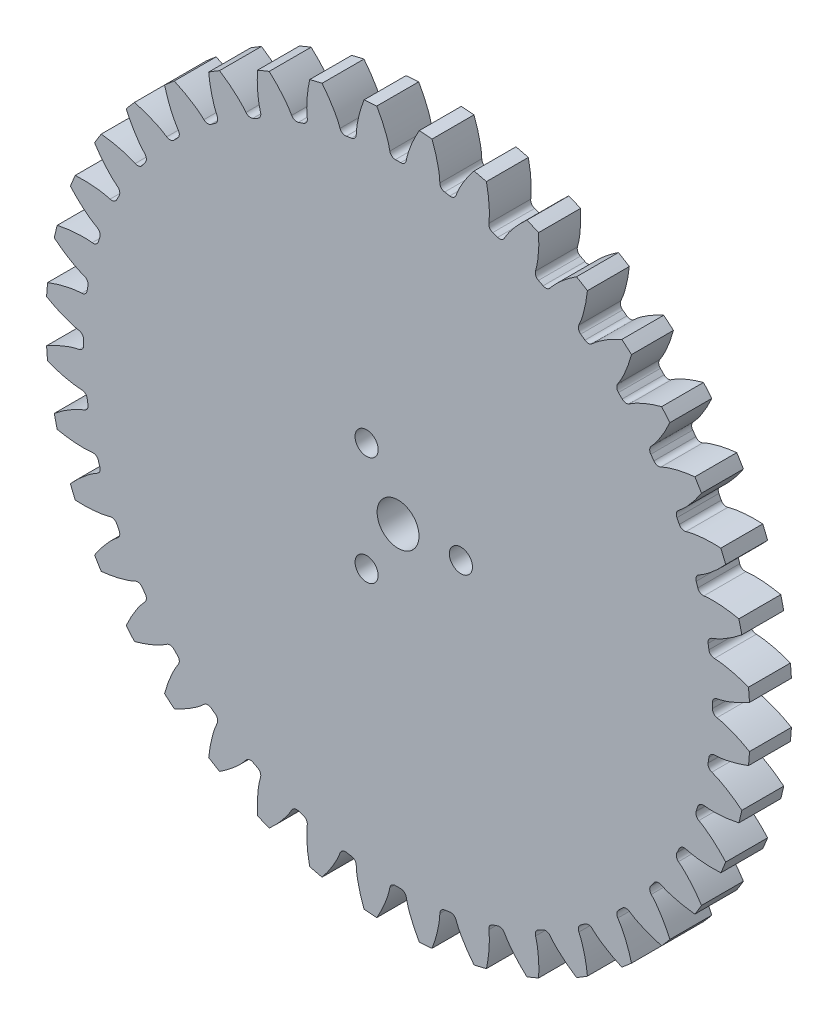
SolidWorks part; units mm, degrees
ref_plane "Front Plane" through (0, 0, 0) normal (0, 0, 1) x (1, 0, 0)
ref_plane "Top Plane" through (0, 0, 0) normal (0, 1, 0) x (1, 0, 0)
ref_plane "Right Plane" through (0, 0, 0) normal (1, 0, 0) x (0, 0, -1)
sketch "Sketch1" plane through (0, 0, 0) normal (0, 0, 1) x (1, 0, 0)
  line L0 (0, 0) -> (0, 50.8) construction
  line L1 (-16.3268, 56.7425) -> (16.3268, 44.8575) construction
  circle A0 centre (0, 0) radius 47.625 construction
  circle A1 centre (0, 0) radius 53.34 construction
  circle A2 centre (0, 0) radius 50.8 construction
  circle A3 centre (0, 0) radius 47.7364 construction
  circle A4 centre (0, 0) radius 3.175 construction
  circle A5 centre (0, 0) radius 37.465 construction
  point P8 (127, 0)
  point P13 (508, 0)
  dimension "OD | Outside Diameter" = 106.68
  dimension "Root Diameter" = 95.25
  dimension "Gear Pitch Diameter" = 101.6
  dimension "Base Diameter" = 95.4728
  dimension "For Shaft Diameter" = 6.35
  dimension "Hub Diameter" = 74.93
  dimension "Pressure Angle" = 20
  dimension "Number of Teeth" = 1016
  dimension "Gear Pitch | Diametral Pitch" = 254
sketch "Sketch2" plane through (0, 0, 0) normal (1, 0, 0) x (0, 0, -1)
  line L0 (-3.175, 0) -> (3.175, 0) construction
  line L1 (-3.175, 53.34) -> (3.175, 53.34) construction
  point P2 (0, 53.34)
  point P4 (-3.175, 0)
  point P6 (-3.175, 53.34)
  dimension "Overall Width" = 6.35
  dimension "Hub Width" = 0
  dimension "Face Width" = 6.35
sketch "Sketch3" plane through (0, 0, 0) normal (0, 0, 1) x (1, 0, 0)
  circle A0 centre (0, 0) radius 53.34
  circle A1 centre (0, 0) radius 53.34 construction
extrude "Boss-Extrude1" add sketch "Sketch3" against normal up to vertex (3.175 mm away) and the other way up to vertex (3.175 mm away) up to point (0, 0, -3.175) other way up to point (0, 0, 3.175)
sketch "Sketch5" plane through (0, 0, 0) normal (1, 0, 0) x (0, 0, -1)
  line L11 (3.175, 3.175) -> (-3.175, 3.175)
  line L12 (3.175, 3.175) -> (3.175, 0)
  line L13 (3.175, 0) -> (-3.175, 0)
  line L14 (-3.175, 3.175) -> (-3.175, 0)
  point P5 (0, 3.175)
sketch "Sketch4" plane through (0, 0, 0) normal (0, 0, 1) x (1, 0, 0)
  line L0 (0, 0) -> (47.6109, 1.1603) construction
  line L2 (0, 0) -> (47.6109, -1.1603) construction
  line L4 (47.6109, 1.1603) -> (47.7222, 1.163)
  line L5 (47.7222, -1.163) -> (47.6109, -1.1603)
  arc A0 (47.6109, 1.1603) -> (47.6109, -1.1603) centre (0, 0) cw
  arc A3 (53.2426, 3.2213) -> (53.2426, -3.2213) centre (0, 0) cw
  circle A4 centre (0, 0) radius 53.34 construction
  spline S0 degree 4 poles (47.7222, 1.163) (47.731, 1.1633) (47.7556, 1.1645) (47.802, 1.1678) (47.8777, 1.1747) (47.9741, 1.186) (48.0986, 1.2033) (48.2451, 1.2271) (48.4058, 1.257) (48.5805, 1.2934) (48.7546, 1.3332) (48.928, 1.3762) (49.1005, 1.4219) (49.3093, 1.4808) (49.5592, 1.5562) (49.8507, 1.6513) (50.1805, 1.7675) (50.5158, 1.8948) (50.845, 2.0273) (51.1768, 2.1695) (51.4972, 2.313) (51.8289, 2.4707) (52.1347, 2.6205) (52.4761, 2.7979) (52.7513, 2.9438) (53.113, 3.1463) (53.3263, 3.2689) (53.5754, 3.4159) (53.6857, 3.483) (53.7537, 3.5243) knots 0 0 0 0 0 0.005377 0.015084 0.028532 0.04661 0.064855 0.092111 0.119476 0.146842 0.174209 0.201575 0.228941 0.256307 0.307035 0.361767 0.4165 0.471232 0.525964 0.580697 0.635429 0.690161 0.744894 0.799626 0.854358 0.909091 0.954545 1 1 1 1 1 construction
  spline S1 degree 4 poles (47.7222, 1.163) (47.731, 1.1633) (47.7556, 1.1645) (47.802, 1.1678) (47.8777, 1.1747) (47.9741, 1.186) (48.0986, 1.2033) (48.2451, 1.2271) (48.4058, 1.257) (48.5805, 1.2934) (48.7546, 1.3332) (48.928, 1.3762) (49.1005, 1.4219) (49.3093, 1.4808) (49.5592, 1.5562) (49.8507, 1.6513) (50.1805, 1.7675) (50.5158, 1.8948) (50.845, 2.0273) (51.1768, 2.1695) (51.4972, 2.313) (51.8289, 2.4707) (52.1347, 2.6205) (52.4761, 2.7979) (52.7513, 2.9438) (53.0346, 3.1024) (53.1723, 3.1808) (53.2426, 3.2213) knots 0 0 0 0 0 0.005377 0.015084 0.028532 0.04661 0.064855 0.092111 0.119476 0.146842 0.174209 0.201575 0.228941 0.256307 0.307035 0.361767 0.4165 0.471232 0.525964 0.580697 0.635429 0.690161 0.744894 0.799626 0.854358 0.909091 0.909091 0.909091 0.909091 0.909091
  spline S2 degree 4 poles (47.7222, -1.163) (47.731, -1.1633) (47.7556, -1.1645) (47.802, -1.1678) (47.8777, -1.1747) (47.9741, -1.186) (48.0986, -1.2033) (48.2451, -1.2271) (48.4058, -1.257) (48.5805, -1.2934) (48.7546, -1.3332) (48.928, -1.3762) (49.1005, -1.4219) (49.3093, -1.4808) (49.5592, -1.5562) (49.8507, -1.6513) (50.1805, -1.7675) (50.5158, -1.8948) (50.845, -2.0273) (51.1768, -2.1695) (51.4972, -2.313) (51.8289, -2.4707) (52.1347, -2.6205) (52.4761, -2.7979) (52.7513, -2.9438) (53.113, -3.1463) (53.3263, -3.2689) (53.5754, -3.4159) (53.6857, -3.483) (53.7537, -3.5243) knots 0 0 0 0 0 0.005377 0.015084 0.028532 0.04661 0.064855 0.092111 0.119476 0.146842 0.174209 0.201575 0.228941 0.256307 0.307035 0.361767 0.4165 0.471232 0.525964 0.580697 0.635429 0.690161 0.744894 0.799626 0.854358 0.909091 0.954545 1 1 1 1 1 construction
  spline S3 degree 4 poles (47.7222, -1.163) (47.731, -1.1633) (47.7556, -1.1645) (47.802, -1.1678) (47.8777, -1.1747) (47.9741, -1.186) (48.0986, -1.2033) (48.2451, -1.2271) (48.4058, -1.257) (48.5805, -1.2934) (48.7546, -1.3332) (48.928, -1.3762) (49.1005, -1.4219) (49.3093, -1.4808) (49.5592, -1.5562) (49.8507, -1.6513) (50.1805, -1.7675) (50.5158, -1.8948) (50.845, -2.0273) (51.1768, -2.1695) (51.4972, -2.313) (51.8289, -2.4707) (52.1347, -2.6205) (52.4761, -2.7979) (52.7513, -2.9438) (53.0346, -3.1024) (53.1723, -3.1808) (53.2426, -3.2213) knots 0 0 0 0 0 0.005377 0.015084 0.028532 0.04661 0.064855 0.092111 0.119476 0.146842 0.174209 0.201575 0.228941 0.256307 0.307035 0.361767 0.4165 0.471232 0.525964 0.580697 0.635429 0.690161 0.744894 0.799626 0.854358 0.909091 0.909091 0.909091 0.909091 0.909091
  dimension "D1" = 95.25
extrude "Cut-Extrude1" cut sketch "Sketch4" against normal through all both and the other way through all
fillet "Fillet1" radius 0.8522 2 edges at (47.6109, -1.1603, 0) (47.6109, 1.1603, 0)
pattern_circular "CirPattern1" count 40 over 360 about axis through (0, 0, 3.175) along (0, 0, -1) of "Cut-Extrude1", "Fillet1"
sketch "Sketch6" plane through (0, 0, 3.175) normal (0, 0, 1) x (1, 0, 0)
  circle A0 centre (9.525, 0) radius 1.75
  circle A1 centre (-4.7625, -8.2489) radius 1.75
  circle A2 centre (-4.7625, 8.2489) radius 1.75
  point P9 (0, 0)
  dimension "D2" = 3.5
  dimension "D1" = 9.525
  dimension "D3" = 3
extrude "Cut-Extrude2" cut sketch "Sketch6" against normal through all
sketch "Sketch7" plane through (0, 0, 3.175) normal (0, 0, 1) x (1, 0, 0)
  circle A0 centre (0, 0) radius 3.175
  dimension "D1" = 6.35
extrude "Cut-Extrude3" cut sketch "Sketch7" against normal through all
equation "\"Root Diameter@Sketch1\"=\"Root Diameter\""
equation "\"OD | Outside Diameter@Sketch1\"=\"Outside Diameter\""
equation "\"D1@CirPattern1\"=\"Number of Teeth\""
equation "\"Diametral Pitch\"= 10"
equation "\"Number of Teeth\"= 40"
equation "\"Pressure Angle\"=20"
equation "\"Pitch Diameter\"= \"Number of Teeth\" / \"Diametral Pitch\""
equation "\"Base Diameter\"= \"Pitch Diameter\" * cos ( \"Pressure Angle\" )"
equation "\"Outside Diameter\"= ( \"Number of Teeth\" + 2 ) / \"Diametral Pitch\""
equation "\"Dedendum\"= 1.25 / \"Diametral Pitch\""
equation "\"Root Diameter\"= \"Pitch Diameter\" - ( 2 * \"Dedendum\" )"
equation "\"Pitch Angle\"= 360deg / \"Number of Teeth\""
equation "\"Alpha\"= sqr ( \"Pitch Diameter\" ^ 2 - \"Base Diameter\" ^ 2 ) / \"Base Diameter\" * 180 / PI - \"Pressure Angle\""
equation "\"Beta\"= ( \"Pitch Angle\" / 4 - \"Alpha\" )"
equation "\"Phi\"= sqr ( ( \"Outside Diameter\" / 2 ) ^ 2 - ( \"Base Diameter\" / 2 ) ^ 2 ) / ( \"Base Diameter\" / 2 )"
equation "\"Addendum\"= 1 / \"Diametral Pitch\""
equation "\"WorkingDepth\"= 2 / \"Diametral Pitch\""
equation "\"WholeDepth\"= 2.25 / \"Diametral Pitch\""
equation "\"Clearance\"= 0.25 / \"Diametral Pitch\""
equation "\"ToothThickness\"= ( pi * 2 ) / \"Diametral Pitch\""
equation "\"CircularPitch\"= pi / \"Diametral Pitch\""
equation "\"Number of Teeth@Sketch1\"=\"Number of Teeth\""
equation "\"Gear Pitch | Diametral Pitch@Sketch1\"=\"Diametral Pitch\""
equation "\"Pressure Angle@Sketch1\"=\"Pressure Angle\""
equation "\"Gear Pitch Diameter@Sketch1\"=\"Pitch Diameter\""
equation "\"Base Diameter@Sketch1\"=\"Base Diameter\""
equation "\"Fillet\"= \"Clearance\" * cos ( \"Pressure Angle\" ) * tan ( ( 90 + \"Pressure Angle\" ) / 2 )"
equation "\"D1@Fillet1\"=\"Fillet\""
equation "\"D1@Sketch4\"=if( \"Base Diameter\">\"Root Diameter\",\"Root Diameter\",\"Base Diameter\"-.00001)"
equation "\"D2@Sketch6\"=3.5mm"
equation "\"tightTol\" = 0.005in"
equation "\"normTol\"= 0.01in"
equation "\"looseTol\"= 0.02in"
equation "\"D1@Sketch7\"=0.250000in"
